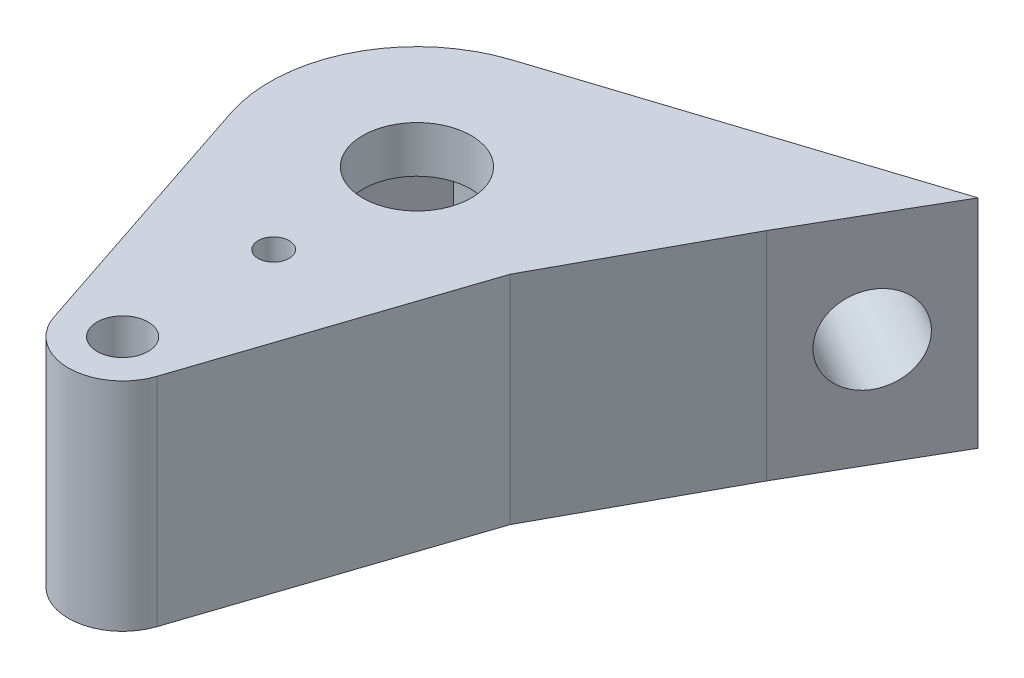
SolidWorks part; units mm, degrees
ref_plane "Front Plane" through (0, 0, 0) normal (0, 0, 1) x (1, 0, 0)
ref_plane "Top Plane" through (0, 0, 0) normal (0, 1, 0) x (1, 0, 0)
ref_plane "Right Plane" through (0, 0, 0) normal (1, 0, 0) x (0, 0, -1)
sketch "Sketch1" plane through (0, 0, 0) normal (0, 1, 0) x (1, 0, 0)
  line L0 (0, 0) -> (0, 28) construction
  line L1 (-9.0139, 25) -> (-3.3209, 7.8947)
  line L2 (-3.2043, 22.45) -> (3.2043, 22.45)
  line L3 (3.2043, 22.45) -> (6.4086, 28)
  line L4 (6.4086, 28) -> (3.2043, 33.55)
  line L5 (3.2043, 33.55) -> (-3.2043, 33.55)
  line L6 (-3.2043, 33.55) -> (-6.4086, 28)
  line L7 (-6.4086, 28) -> (-3.2043, 22.45)
  line L8 (9.0139, 25) -> (3.3209, 7.8947)
  line L9 (0, 0) -> (24.1291, 41.7929) construction
  line L10 (0, 28) -> (0, 29.75) construction
  line L11 (0, 29.75) -> (17.1762, 29.75) construction
  line L12 (14.846, 35.7141) -> (19.846, 44.3744)
  line L13 (21.1451, 43.6244) -> (27.2073, 40.1244) construction
  line L14 (21.1451, 43.6244) -> (16.1451, 34.9641) construction
  line L15 (16.1451, 34.9641) -> (22.2073, 31.4641) construction
  line L16 (27.2073, 40.1244) -> (22.2073, 31.4641) construction
  line L17 (21.1451, 43.6244) -> (22.2073, 31.4641) construction
  line L18 (16.1451, 34.9641) -> (27.2073, 40.1244) construction
  line L19 (14.846, 35.7141) -> (16.1451, 34.9641) construction
  line L20 (19.846, 44.3744) -> (21.1451, 43.6244) construction
  line L21 (9.0139, 25) -> (14.846, 35.7141)
  line L22 (19.846, 44.3744) -> (-2.9131, 37.0424)
  circle A0 centre (0, 28) radius 5.55 construction
  circle A2 centre (0, 9) radius 1.65
  arc A3 (-3.3209, 7.8947) -> (3.3209, 7.8947) centre (0, 9) ccw
  arc A4 (-2.9131, 37.0424) -> (-9.0139, 25) centre (0, 28) ccw
  arc A5 (0, 12.5) -> (-3.3209, 7.8947) centre (0, 9) ccw construction
  arc A6 (3.3209, 7.8947) -> (0, 12.5) centre (0, 9) ccw construction
  arc A7 (-9.0139, 25) -> (0, 18.5) centre (0, 28) ccw construction
  arc A8 (0, 18.5) -> (9.0139, 25) centre (0, 28) ccw construction
  circle A10 centre (17.1762, 29.75) radius 1.7 construction
  circle A11 centre (21.6762, 37.5442) radius 1.7 construction
  arc A12 (9.0139, 25) -> (9.3374, 29.75) centre (0, 28) ccw construction
  arc A13 (9.3374, 29.75) -> (-2.9131, 37.0424) centre (0, 28) ccw construction
  circle A14 centre (0, 18.75) radius 1
  point P32 (0, 22.45)
  dimension "D2" = 11.1
  dimension "D3" = 9
  dimension "D4" = 3.3
  dimension "D5" = 7
  dimension "D6" = 19
  dimension "D8" = 9
  dimension "D9" = 3.4
  dimension "D13" = 2
  dimension "D1" = 28
  dimension "D7" = 30
  dimension "D10" = 1.75
  dimension "D11" = 7
  dimension "D12" = 1.5
  dimension "D14" = 9.25
  dimension "D15" = 10
extrude "Boss-Extrude1" add sketch "Sketch1" along normal blind 14
sketch "Sketch2" plane through (0, 14, 0) normal (0, 1, 0) x (1, 0, 0)
  line L1 (0, 33.55) -> (0, 22.45) construction
  line L7 (-3.2043, 22.45) -> (3.2043, 22.45)
  line L8 (-6.4086, 28) -> (-3.2043, 22.45)
  line L9 (-3.2043, 33.55) -> (-6.4086, 28)
  line L10 (3.2043, 33.55) -> (-3.2043, 33.55)
  line L11 (6.4086, 28) -> (3.2043, 33.55)
  line L12 (3.2043, 22.45) -> (6.4086, 28)
  line L13 (-3.2043, 22.45) -> (3.2043, 22.45)
  line L14 (-6.4086, 28) -> (-3.2043, 22.45)
  line L15 (-3.2043, 33.55) -> (-6.4086, 28)
  line L16 (3.2043, 33.55) -> (-3.2043, 33.55)
  line L17 (6.4086, 28) -> (3.2043, 33.55)
  line L18 (3.2043, 22.45) -> (6.4086, 28)
  circle A0 centre (0, 28) radius 3.5
  dimension "D2" = 7
  dimension "D1" = 0
extrude "Boss-Extrude2" add sketch "Sketch2" against normal blind 3 contours L13 L18 L17 L16 L15 L14 | A0
sketch "Sketch3" plane through (-4.3301, 0, -2.5) normal (0.866, 0, 0.5) x (0.5, 0, -0.866)
  line L0 (43.3523, 14) -> (43.3523, 0) construction
  line L1 (38.3523, 14) -> (48.3523, 14) construction
  line L2 (38.3523, 0) -> (48.3523, 0) construction
  circle A0 centre (43.3523, 7) radius 2.8
  dimension "D1" = 5.6
extrude "Cut-Extrude1" cut sketch "Sketch3" against normal through all
sketch "Sketch4" plane through (-4.3301, 0, -2.5) normal (0.866, 0, 0.5) x (0.5, 0, -0.866)
  circle A0 centre (43.3523, 7) radius 4.5
  circle A1 centre (43.3523, 7) radius 2.8
  circle A2 centre (43.3523, 7) radius 2.8
  dimension "D2" = 9
  dimension "D1" = 0
extrude "Boss-Extrude3" add sketch "Sketch4" against normal blind 8
fillet "Fillet1" radius 1 1 edges at (12.6678, 7, -47.9413)
ref_axis "Axis1" through (0, 14, -18.75) along (0, -1, 0)
ref_plane "Plane1" through (-5.3773, 0, -1.6954) normal (-0.9537, 0, -0.3007) x (0, -1, 0)
sketch "Sketch5" plane through (-5.3773, 0, -1.6954) normal (-0.9537, 0, -0.3007) x (0, -1, 0)
  line L0 (-14, -17.8822) -> (0, -17.8822) construction
  line L1 (-14, -16.8822) -> (-14, -18.8822) construction
  line L2 (0, -18.8822) -> (0, -16.8822) construction
  circle A0 centre (-7, -17.8822) radius 2
  dimension "D1" = 4
extrude "Cut-Extrude2" cut sketch "Sketch5" along normal through all
